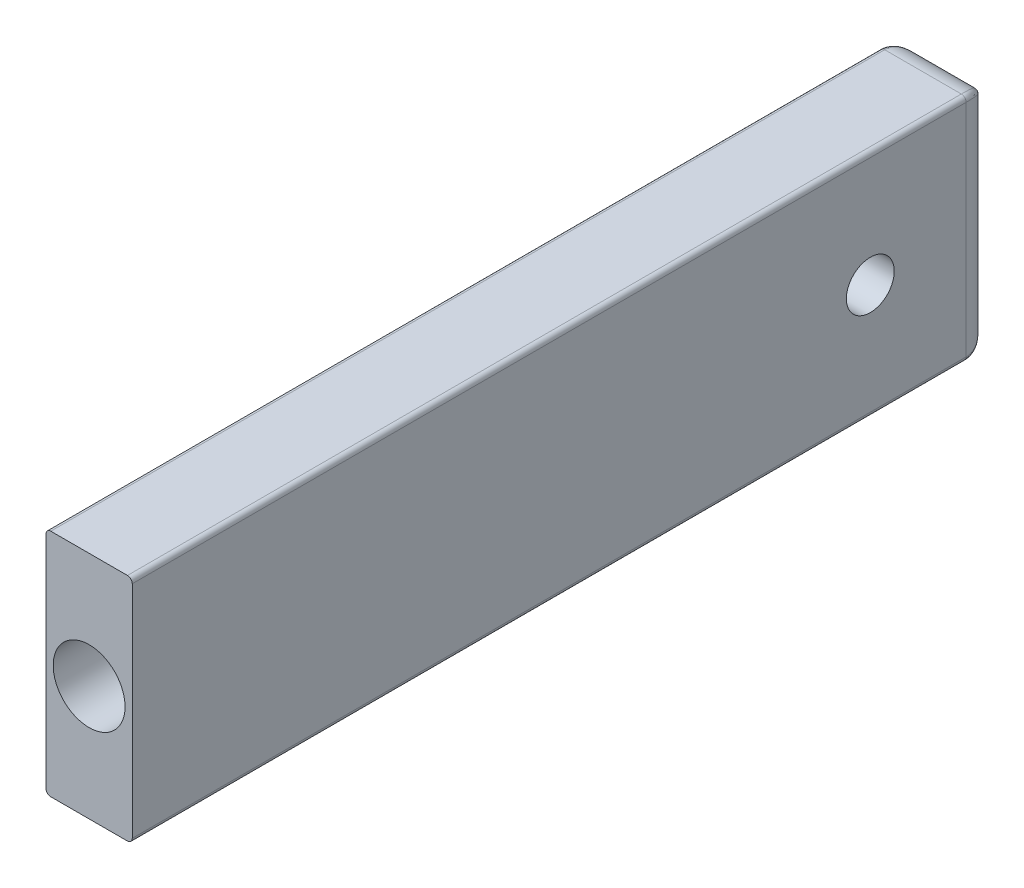
SolidWorks part; units mm, degrees
material "PLA"
ref_plane "Front" through (0, 0, 0) normal (0, 0, 1) x (1, 0, 0)
ref_plane "Top" through (0, 0, 0) normal (0, 1, 0) x (1, 0, 0)
ref_plane "Right" through (0, 0, 0) normal (1, 0, 0) x (0, 0, -1)
sketch "Sketch1" plane through (0, 0, -18.0919) normal (0, 0, -1) x (-1, 0, 0)
  line L0 (-10.922, -29.464) -> (-10.922, -35.306)
  line L1 (-10.795, -35.433) -> (-8.763, -35.433)
  line L2 (-8.636, -35.306) -> (-8.636, -29.464)
  line L3 (-8.763, -29.337) -> (-10.795, -29.337)
  line L4 (-11.049, -29.464) -> (-11.049, -35.306)
  line L5 (-10.795, -35.56) -> (-8.763, -35.56)
  line L6 (-8.509, -35.306) -> (-8.509, -29.464)
  line L7 (-8.763, -29.21) -> (-10.795, -29.21)
  line L8 (-11.049, -29.464) -> (-11.049, -35.306)
  line L9 (-10.795, -35.56) -> (-8.763, -35.56)
  line L10 (-8.509, -35.306) -> (-8.509, -29.464)
  line L11 (-8.763, -29.21) -> (-10.795, -29.21)
  arc A0 (-10.795, -29.337) -> (-10.922, -29.464) centre (-10.795, -29.464) ccw
  arc A1 (-10.922, -35.306) -> (-10.795, -35.433) centre (-10.795, -35.306) ccw
  arc A2 (-8.763, -35.433) -> (-8.636, -35.306) centre (-8.763, -35.306) ccw
  arc A3 (-8.636, -29.464) -> (-8.763, -29.337) centre (-8.763, -29.464) ccw
  arc A4 (-10.795, -29.21) -> (-11.049, -29.464) centre (-10.795, -29.464) ccw
  arc A5 (-11.049, -35.306) -> (-10.795, -35.56) centre (-10.795, -35.306) ccw
  arc A6 (-8.763, -35.56) -> (-8.509, -35.306) centre (-8.763, -35.306) ccw
  arc A7 (-8.509, -29.464) -> (-8.763, -29.21) centre (-8.763, -29.464) ccw
  arc A8 (-10.795, -29.21) -> (-11.049, -29.464) centre (-10.795, -29.464) ccw
  arc A9 (-11.049, -35.306) -> (-10.795, -35.56) centre (-10.795, -35.306) ccw
  arc A10 (-8.763, -35.56) -> (-8.509, -35.306) centre (-8.763, -35.306) ccw
  arc A11 (-8.509, -29.464) -> (-8.763, -29.21) centre (-8.763, -29.464) ccw
  dimension "D1" = 0
  dimension "D2" = 0.127
extrude "Boss-Extrude1" add sketch "Sketch1" along normal offset from surface (22.86 mm away) 6.35 contours A0 L0 A1 L1 A2 L2 A3 L3 offset beyond the face yes
sketch "Sketch2" plane through (0, 0, -18.0919) normal (0, 0, 1) x (1, 0, 0)
  circle A0 centre (9.779, -32.385) radius 0.9525
extrude "Cut-Extrude1" cut sketch "Sketch2" against normal blind 7.62
fillet "Fillet1" radius 0.762 8 edges at (10.8848, -35.3958, -40.9519) (10.8848, -29.3742, -40.9519) (8.6732, -29.3742, -40.9519) (8.6732, -35.3958, -40.9519) (8.636, -32.385, -40.9519) (9.779, -29.337, -40.9519) (10.922, -32.385, -40.9519) (9.779, -35.433, -40.9519)
sketch "Sketch3" plane through (10.922, 0, 0) normal (1, 0, 0) x (0, 0, -1)
  line L3 (40.1899, -29.464) -> (18.0919, -29.464) construction
  line L5 (40.1899, -35.306) -> (40.1899, -29.464) construction
  circle A0 centre (37.6499, -32.385) radius 0.635
  dimension "D1" = 2.921
  dimension "D2" = 1.27
  dimension "D3" = 2.54
extrude "Cut-Extrude2" cut sketch "Sketch3" against normal through all
